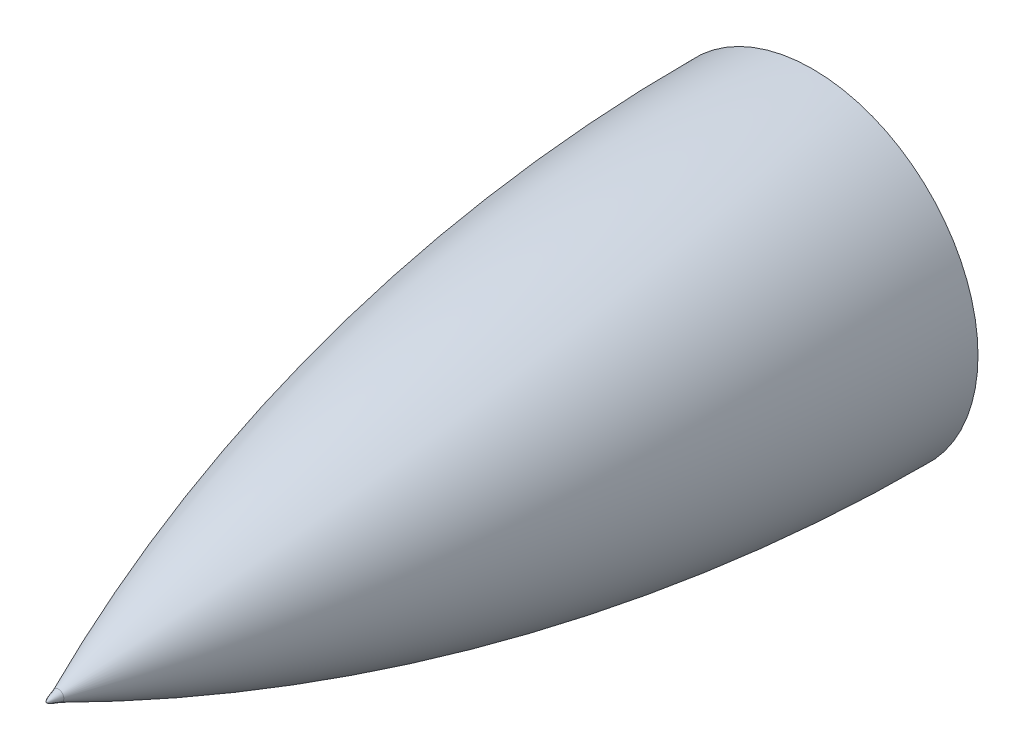
SolidWorks part; units mm, degrees
ref_plane "Front Plane" through (0, 0, 0) normal (0, 0, 1) x (1, 0, 0)
ref_plane "Top Plane" through (0, 0, 0) normal (0, 1, 0) x (1, 0, 0)
ref_plane "Right Plane" through (0, 0, 0) normal (1, 0, 0) x (0, 0, -1)
sketch "Sketch1" plane through (0, 0, 0) normal (1, 0, 0) x (0, 0, -1)
  line L0 (0, 0) -> (0, 419.7439) construction
  line L1 (-190, 419.7439) -> (0, 419.7439) construction
  line L2 (0, 460.7439) -> (0, 459.2439)
  line L5 (0, 459.2439) -> (0, 460.7439) construction
  line L9 (-190, 419.7439) -> (-182.6049, 419.7439)
  line L11 (-190, 419.7439) -> (0, 419.7439)
  line L12 (-54, 454.5476) -> (-54, 456.0581)
  line L13 (-3, 457.7341) -> (-3, 454.7439) construction
  line L14 (0, 457.7439) -> (82, 457.7439) construction
  line L15 (0, 460.7439) -> (0, 457.7439) construction
  line L16 (-3, 454.7439) -> (79, 454.7439) construction
  line L17 (82, 457.7439) -> (82, 419.7439) construction
  line L18 (79, 454.7439) -> (79, 419.7439) construction
  arc A0 (0, 460.7439) -> (-190, 419.7439) centre (0, 0) ccw
  arc A1 (-54, 454.5476) -> (-182.6049, 419.7439) centre (0, 0) ccw
  arc A2 (-3, 457.7341) -> (-188.7629, 417.0109) centre (0, 0) ccw construction
  arc A3 (0, 459.2439) -> (-54, 456.0581) centre (0, 0) ccw
  arc A4 (0, 459.2439) -> (-189.3814, 418.3774) centre (0, 0) ccw construction
  dimension "D1" = 190
  dimension "D2" = 41
  dimension "D6" = 3
revolve "Revolve2" add sketch "Sketch1" angle 360 about L1
sketch "Sketch2" plane through (0, 0, 0) normal (1, 0, 0) x (0, 0, -1)
  line L0 (-190, 419.7439) -> (-187, 419.7439)
  line L1 (-187, 419.7439) -> (-187, 421.089)
  arc A0 (0, 460.7439) -> (-190, 419.7439) centre (0, 0) ccw construction
  arc A1 (-187, 421.089) -> (-190, 419.7439) centre (0, 0) ccw
  dimension "D1" = 3
revolve "Cut-Revolve1" cut sketch "Sketch2" angle 360 about L0
sketch "Sketch3" plane through (0, 0, 0) normal (1, 0, 0) x (0, 0, -1)
  line L0 (-187, 419.7439) -> (-190, 419.7439)
  line L1 (-187, 421.089) -> (-187, 418.3988) construction
  line L3 (-187, 421.089) -> (-187, 418.3988)
  spline S0 degree 3 poles (-187, 421.089) (-188.1232, 420.7132) (-189.9306, 420.2524) (-190, 419.7439) knots 0 0 0 0 0.5 0.5 0.5 0.5
  dimension "D1" = 3
revolve "Revolve3" add sketch "Sketch3" angle 360 about L0
